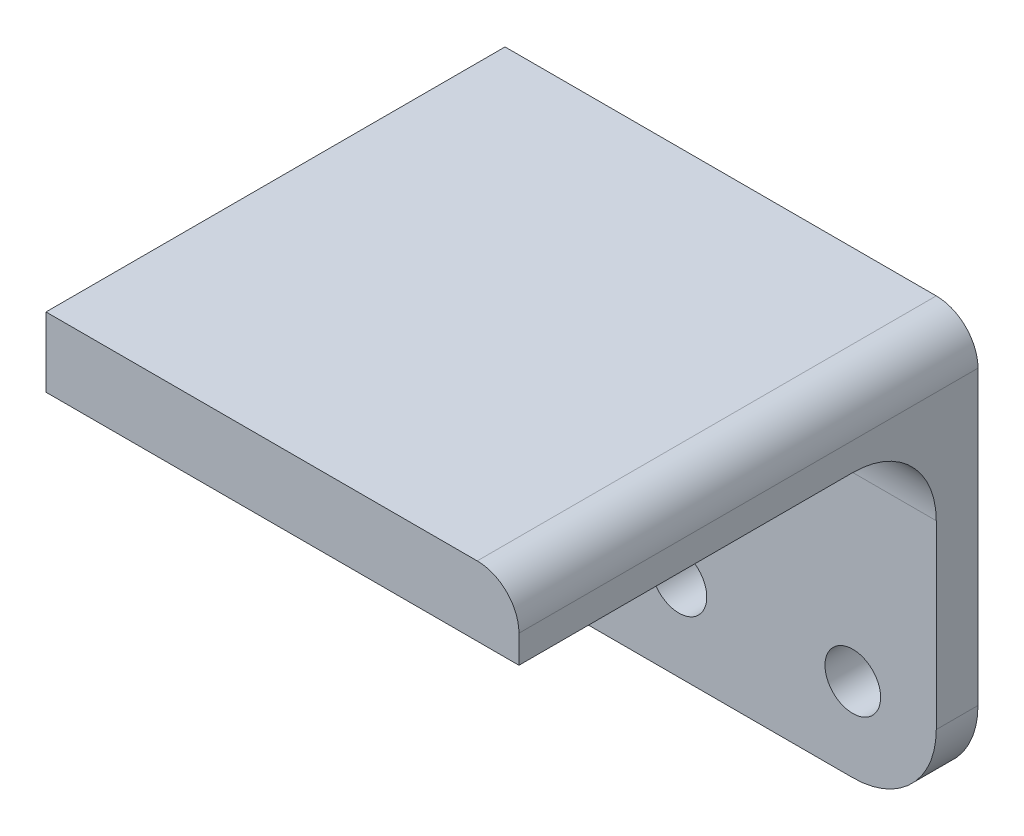
SolidWorks part; units mm, degrees
ref_plane "Plan de face" through (0, 0, 0) normal (0, 0, 1) x (1, 0, 0)
ref_plane "Plan de dessus" through (0, 0, 0) normal (0, 1, 0) x (1, 0, 0)
ref_plane "Plan de droite" through (0, 0, 0) normal (1, 0, 0) x (0, 0, -1)
sketch "Esquisse1" plane through (0, 0, 0) normal (0, 0, 1) x (1, 0, 0)
  line L0 (-5, 1.5) -> (23, 1.5)
  line L1 (-11, 7.5) -> (-11, 28.5)
  line L2 (23, 1.5) -> (23, 31.5)
  line L3 (-8, 31.5) -> (23, 31.5)
  line L11 (14, 23.5) -> (17, 23.5)
  line L13 (17, 19.5) -> (14, 19.5)
  circle A0 centre (-5, 7.5) radius 2
  circle A1 centre (7.5, 7.5) radius 2
  arc A2 (14, 23.5) -> (14, 19.5) centre (14, 21.5) ccw
  arc A3 (-5, 1.5) -> (-11, 7.5) centre (-5, 7.5) cw
  arc A4 (-11, 28.5) -> (-8, 31.5) centre (-8, 28.5) cw
  arc A7 (17, 19.5) -> (17, 23.5) centre (17, 21.5) ccw
  point P10 (-11, 1.5)
  point P13 (-11, 31.5)
  point P156 (0, 0)
  dimension "D2" = 3
  dimension "D7" = 6
  dimension "D12" = 4
  dimension "D10" = 6
  dimension "D11" = 3
  dimension "D3" = 6.5
  dimension "D4" = 14
  dimension "D5" = 12.5
  dimension "D6" = 6
  dimension "D8" = 30
  dimension "D9" = 6
extrude "Boss.-Extru.1" add sketch "Esquisse1" along normal blind 3
sketch "Esquisse2" plane through (0, 0, 3) normal (0, 0, 1) x (1, 0, 0)
  line L1 (-11, 28.5) -> (-11, 7.5) construction
  line L2 (23, 31.5) -> (-8, 31.5)
  line L3 (23, 31.5) -> (23, 26.5)
  line L4 (23, 26.5) -> (-11, 26.5)
  line L5 (-11, 28.5) -> (-11, 26.5)
  line L6 (23, 31.5) -> (-11, 26.5) construction
  line L7 (23, 26.5) -> (-11, 31.5) construction
  arc A0 (-8, 31.5) -> (-11, 28.5) centre (-8, 28.5) ccw
  point P16 (6, 29)
  dimension "D2" = 3
  dimension "D1" = 5
extrude "Boss.-Extru.2" add sketch "Esquisse2" along normal blind 30 contours L2 L5 L4 L3 region at (6.1877, 28.979, 3)
fillet "Congé1" radius 6 1 edges at (6, 26.5, 3)
mirror "Symétrie1" about plane through (23, 1.5, 3) normal (-1, 0, 0) of "Boss.-Extru.2", "Congé1", "Boss.-Extru.1"
sketch "Esquisse3" plane through (0, 0, 33) normal (0, 0, 1) x (1, 0, 0)
  line L0 (23, 26.5) -> (23, 20.5) construction
  line L1 (-14.3815, 39.8441) -> (23, 39.8441)
  line L2 (-14.3815, 39.8441) -> (-14.3815, -8.4727)
  line L3 (-14.3815, -8.4727) -> (23, -8.4727)
  line L4 (23, 39.8441) -> (23, -8.4727)
  line L5 (-14.3815, 39.8441) -> (23, -8.4727) construction
  line L6 (-14.3815, -8.4727) -> (23, 39.8441) construction
  point P4 (4.3092, 15.6857)
extrude "Enlèv. mat.-Extru.1" cut sketch "Esquisse3" against normal through all both and the other way through all
